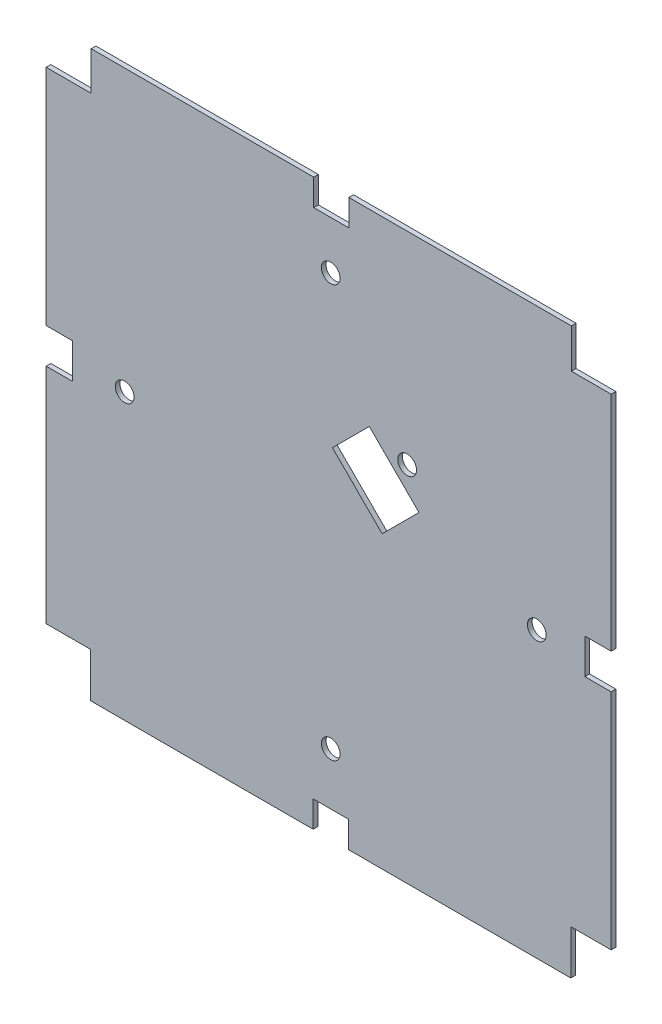
SolidWorks part; units mm, degrees
ref_plane "Front Plane" through (0, 0, 0) normal (0, 0, 1) x (1, 0, 0)
ref_plane "Top Plane" through (0, 0, 0) normal (0, 1, 0) x (1, 0, 0)
ref_plane "Right Plane" through (0, 0, 0) normal (1, 0, 0) x (0, 0, -1)
sketch "Sketch1" plane through (0, 0, 0) normal (0, 0, 1) x (1, 0, 0)
  line L1 (-67.0283, 35.647) -> (29.4717, 35.647)
  line L2 (-67.0283, 35.647) -> (-67.0283, -60.853)
  line L3 (-67.0283, -60.853) -> (29.4717, -60.853)
  line L4 (29.4717, 35.647) -> (29.4717, -60.853)
  line L5 (-67.0283, 35.647) -> (-59.3283, 35.647)
  line L6 (-67.0283, 35.647) -> (-67.0283, 29.047)
  line L7 (-67.0283, 29.047) -> (-59.3283, 29.047)
  line L8 (-59.3283, 35.647) -> (-59.3283, 29.047)
  line L21 (-67.0283, -9.153) -> (-62.5283, -9.153)
  line L22 (-67.0283, -9.153) -> (-67.0283, -15.153)
  line L23 (-67.0283, -15.153) -> (-62.5283, -15.153)
  line L24 (-62.5283, -9.153) -> (-62.5283, -15.153)
  line L25 (29.4717, 35.647) -> (22.6717, 35.647)
  line L26 (29.4717, 35.647) -> (29.4717, 28.947)
  line L27 (29.4717, 28.947) -> (22.6717, 28.947)
  line L28 (22.6717, 35.647) -> (22.6717, 28.947)
  line L29 (29.4717, -15.073) -> (24.9717, -15.073)
  line L30 (29.4717, -15.073) -> (29.4717, -9.073)
  line L31 (29.4717, -9.073) -> (24.9717, -9.073)
  line L32 (24.9717, -15.073) -> (24.9717, -9.073)
  line L33 (29.4717, -60.853) -> (22.5717, -60.853)
  line L34 (29.4717, -60.853) -> (29.4717, -53.253)
  line L35 (29.4717, -53.253) -> (22.5717, -53.253)
  line L36 (22.5717, -60.853) -> (22.5717, -53.253)
  line L37 (-67.0283, -60.853) -> (-59.4283, -60.853)
  line L38 (-67.0283, -60.853) -> (-67.0283, -53.253)
  line L39 (-67.0283, -53.253) -> (-59.4283, -53.253)
  line L40 (-59.4283, -60.853) -> (-59.4283, -53.253)
  line L42 (-21.3283, 35.647) -> (-15.3283, 35.647)
  line L43 (-21.3283, 35.647) -> (-21.3283, 31.147)
  line L44 (-21.3283, 31.147) -> (-15.3283, 31.147)
  line L45 (-15.3283, 35.647) -> (-15.3283, 31.147)
  line L47 (-21.4283, -60.853) -> (-15.4283, -60.853)
  line L48 (-21.4283, -60.853) -> (-21.4283, -56.353)
  line L49 (-21.4283, -56.353) -> (-15.4283, -56.353)
  line L50 (-15.4283, -60.853) -> (-15.4283, -56.353)
  circle A0 centre (16.7687, -12.2528) radius 1.6
  circle A1 centre (-18.4281, 22.944) radius 1.6
  circle A2 centre (-18.4281, -47.4496) radius 1.6
  circle A3 centre (-53.625, -12.2528) radius 1.6
  circle A4 centre (-5.3709, 1.097) radius 1.6
  circle A5 centre (16.7687, -12.2528) radius 1.7 construction
  circle A6 centre (-53.625, -12.2528) radius 1.7 construction
  circle A7 centre (-18.4281, 22.944) radius 1.7 construction
  circle A8 centre (-18.4281, -47.4496) radius 1.7 construction
  dimension "D17" = 3.2
  dimension "D19" = 3.2
  dimension "D20" = 3.2
  dimension "D21" = 3.2
  dimension "D27" = 3.2
  dimension "D16" = 0
  dimension "D22" = 0
  dimension "D1" = 96.5
  dimension "D2" = 96.5
  dimension "D3" = 4.5
  dimension "D4" = 7.7
  dimension "D5" = 6.6
  dimension "D6" = 6
  dimension "D7" = 45.7
  dimension "D8" = 7.6
  dimension "D9" = 7.6
  dimension "D10" = 6.9
  dimension "D11" = 7.6
  dimension "D12" = 6
  dimension "D13" = 4.5
  dimension "D14" = 6.7
  dimension "D15" = 6.8
  dimension "D18" = 0
  dimension "D25" = 0
  dimension "D28" = 4.5
  dimension "D29" = 6
  dimension "D30" = 45.7
  dimension "D33" = 4.5
  dimension "D34" = 6
  dimension "D35" = 45.6
extrude "Boss-Extrude1" add sketch "Sketch1" along normal blind 0.8 contours L40 L3 L36 L35 L4 L29 L32 L31 L27 L28 L1 L8 L7 L2 L21 L24 L23 L39 A4 A3 A2 A1 A0 region at (-18.7459, -12.556, 0)
sketch "Sketch2" plane through (0, 0, 0.8) normal (0, 0, 1) x (1, 0, 0)
  line L0 (-11.8377, 3.523) -> (-3.3524, -4.9623)
  line L1 (-11.8377, 3.523) -> (-18.1309, -2.7703)
  line L2 (-3.3524, -4.9623) -> (-9.6457, -11.2556)
  line L3 (-18.1309, -2.7703) -> (-9.6457, -11.2556)
  line L4 (-16.4205, -1.0599) -> (-7.9353, -9.5452)
  line L5 (-5.0361, -6.646) -> (-13.5214, 1.8392)
  line L6 (-59.4283, -60.853) -> (-21.4283, -60.853) construction
  line L7 (-67.0283, -15.153) -> (-67.0283, -53.253) construction
  point P10 (-10.7283, -3.853)
  dimension "D1" = 45
  dimension "D2" = 8.9
  dimension "D3" = 12
  dimension "D4" = 4.1
  dimension "D5" = 2.05
  dimension "D6" = 6
  dimension "D7" = 56.3
  dimension "D8" = 57
extrude "Cut-Extrude1" cut sketch "Sketch2" against normal blind 0.8 contours L4 L1 L3 L2 | L2 L5 L1 L4 | L5 L2 L0 L1 region at (-8.4369, -1.5615, 0.8) region at (-10.7283, -3.853, 0.8) region at (-13.0331, -6.1577, 0.8)
equation "\"D5@Sketch2\"=\"D4@Sketch2\"/2"
equation "\"D6@Sketch2\"=\"D3@Sketch2\"/2"
